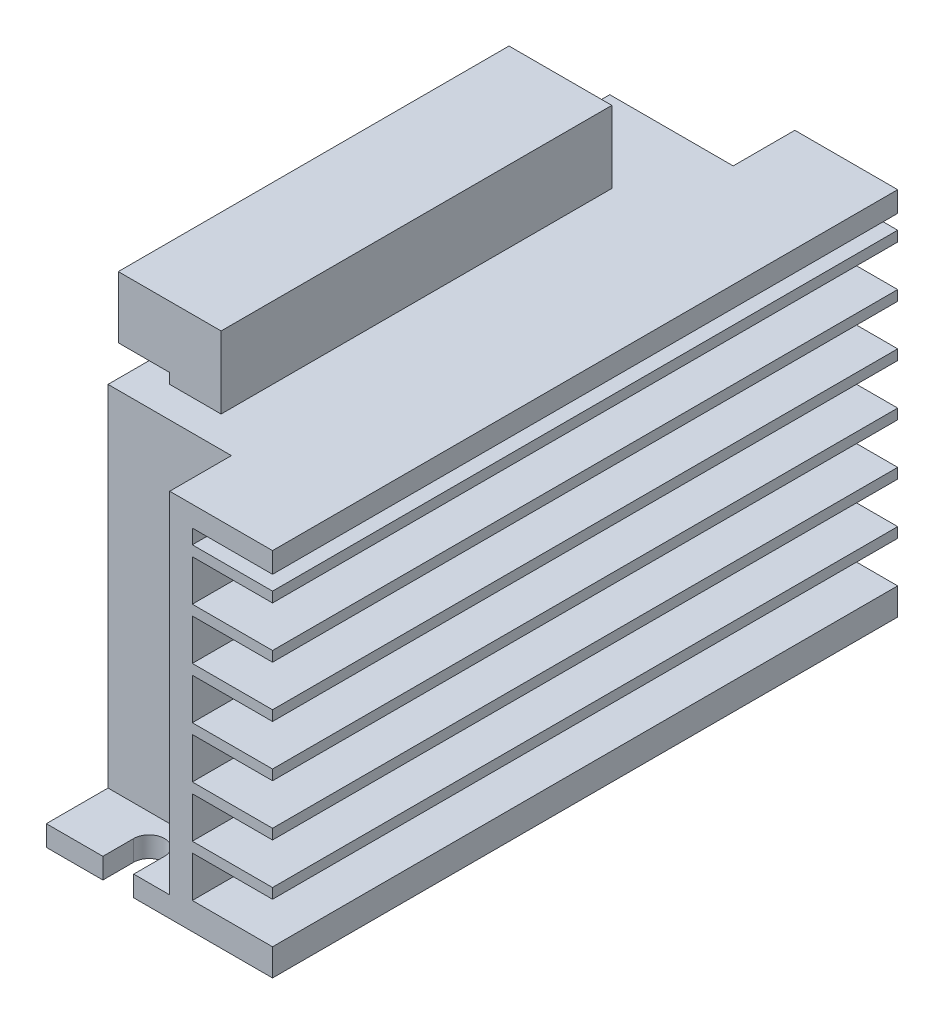
SolidWorks part; units mm, degrees
ref_plane "Front Plane" through (0, 0, 0) normal (0, 0, 1) x (1, 0, 0)
ref_plane "Top Plane" through (0, 0, 0) normal (0, 1, 0) x (1, 0, 0)
ref_plane "Right Plane" through (0, 0, 0) normal (1, 0, 0) x (0, 0, -1)
sketch "Sketch1" plane through (0, 0, 0) normal (0, 1, 0) x (1, 0, 0)
  line L0 (11.1125, 86.5187) -> (11.1125, 4.7625) construction
  line L1 (0, 0) -> (8.7313, 0)
  line L2 (0, 0) -> (0, 96.52)
  line L3 (0, 96.52) -> (8.7312, 96.52)
  line L4 (34.925, 0) -> (34.925, 96.52)
  line L5 (13.4937, 0) -> (34.925, 0)
  line L7 (8.7312, 91.7575) -> (8.7312, 96.52)
  line L9 (13.4937, 91.7575) -> (13.4937, 96.52)
  line L11 (8.7313, 4.7625) -> (8.7313, 0)
  line L13 (13.4937, 4.7625) -> (13.4937, 0)
  line L14 (13.4937, 96.52) -> (34.925, 96.52)
  arc A0 (8.7312, 91.7575) -> (13.4937, 91.7575) centre (11.1125, 91.7575) ccw
  arc A1 (13.4937, 4.7625) -> (8.7313, 4.7625) centre (11.1125, 4.7625) ccw
  dimension "D3" = 4.7625
  dimension "D6" = 4.7625
  dimension "D1" = 96.52
  dimension "D2" = 34.925
  dimension "D4" = 11.1125
  dimension "D5" = 4.7625
extrude "Boss-Extrude1" add sketch "Sketch1" along normal blind 57.15
sketch "Sketch2" plane through (0, 0, 0) normal (0, 0, 1) x (1, 0, 0)
  line L0 (13.4937, 0) -> (34.925, 0) construction
  line L1 (0, 57.15) -> (19.05, 57.15)
  line L2 (0, 57.15) -> (0, 3.175)
  line L3 (0, 3.175) -> (19.05, 3.175)
  line L4 (19.05, 57.15) -> (19.05, 3.175)
  dimension "D1" = 3.175
  dimension "D2" = 19.05
extrude "Cut-Extrude1" cut sketch "Sketch2" against normal blind 9.525
sketch "Sketch4" plane through (0, 0, -96.52) normal (0, 0, -1) x (-1, 0, 0)
  line L0 (0, 57.15) -> (0, 0) construction
  line L1 (0, 3.175) -> (-19.05, 3.175)
  line L2 (0, 3.175) -> (0, 57.15)
  line L3 (0, 57.15) -> (-19.05, 57.15)
  line L4 (-19.05, 3.175) -> (-19.05, 57.15)
  line L5 (-34.925, 57.15) -> (-13.4937, 57.15) construction
  line L6 (-34.925, 0) -> (-13.4937, 0) construction
  dimension "D1" = 3.175
  dimension "D2" = 19.05
extrude "Cut-Extrude2" cut sketch "Sketch4" against normal blind 9.525
sketch "Sketch5" plane through (0, 0, -96.52) normal (0, 0, -1) x (-1, 0, 0)
  line L0 (-34.925, 57.15) -> (-34.925, 0) construction
  line L1 (-34.925, 4.1741) -> (-22.5404, 4.1741)
  line L2 (-34.925, 4.1741) -> (-34.925, 10.5241)
  line L3 (-34.925, 10.5241) -> (-22.5404, 10.5241)
  line L4 (-22.5404, 4.1741) -> (-22.5404, 10.5241)
  line L5 (-28.7327, 0) -> (-28.7327, 57.15) construction
  line L6 (-34.925, 0) -> (-13.4937, 0) construction
  line L7 (-34.925, 57.15) -> (-19.05, 57.15) construction
  line L8 (-34.925, 18.4478) -> (-22.5404, 18.4478)
  line L9 (-34.925, 12.0978) -> (-34.925, 18.4478)
  line L10 (-34.925, 12.0978) -> (-22.5404, 12.0978)
  line L11 (-22.5404, 12.0978) -> (-22.5404, 18.4478)
  line L12 (-34.925, 26.3715) -> (-22.5404, 26.3715)
  line L13 (-34.925, 20.0215) -> (-34.925, 26.3715)
  line L14 (-34.925, 20.0215) -> (-22.5404, 20.0215)
  line L15 (-22.5404, 20.0215) -> (-22.5404, 26.3715)
  line L16 (-34.925, 34.2952) -> (-22.5404, 34.2952)
  line L17 (-34.925, 27.9452) -> (-34.925, 34.2952)
  line L18 (-34.925, 27.9452) -> (-22.5404, 27.9452)
  line L19 (-22.5404, 27.9452) -> (-22.5404, 34.2952)
  line L20 (-34.925, 42.2189) -> (-22.5404, 42.2189)
  line L21 (-34.925, 35.8689) -> (-34.925, 42.2189)
  line L22 (-34.925, 35.8689) -> (-22.5404, 35.8689)
  line L23 (-22.5404, 35.8689) -> (-22.5404, 42.2189)
  line L24 (-34.925, 50.1426) -> (-22.5404, 50.1426)
  line L25 (-34.925, 43.7926) -> (-34.925, 50.1426)
  line L26 (-34.925, 43.7926) -> (-22.5404, 43.7926)
  line L27 (-22.5404, 43.7926) -> (-22.5404, 50.1426)
  line L29 (-34.925, 51.7301) -> (-22.5404, 51.7301)
  line L30 (-34.925, 51.7301) -> (-34.925, 53.975)
  line L31 (-34.925, 53.975) -> (-22.5404, 53.975)
  line L32 (-22.5404, 51.7301) -> (-22.5404, 53.975)
  dimension "D1" = 6.35
  dimension "D2" = 3.175
  dimension "D3" = 6
  dimension "D4" = 1.5875
extrude "Cut-Extrude3" cut sketch "Sketch5" against normal up to surface (96.52 mm away) up to face at (22.4896, 20.1083, 0)
sketch "Sketch6" plane through (0, 57.15, 0) normal (0, 1, 0) x (1, 0, 0)
  line L0 (0, 86.995) -> (0, 9.525) construction
  line L1 (4.7625, 74.6106) -> (12.7, 74.6106)
  line L2 (4.7625, 74.6106) -> (4.7625, 14.2856)
  line L3 (4.7625, 14.2856) -> (12.7, 14.2856)
  line L4 (12.7, 74.6106) -> (12.7, 14.2856)
  line L5 (34.925, 48.26) -> (0, 48.26) construction
  line L6 (34.925, 0) -> (34.925, 96.52) construction
  line L7 (4.7625, 44.4481) -> (12.7, 44.4481) construction
  dimension "D1" = 7.9375
  dimension "D2" = 60.325
  dimension "D3" = 4.7625
extrude "Boss-Extrude2" add sketch "Sketch6" along normal blind 1.5875
sketch "Sketch7" plane through (0, 58.7375, 0) normal (0, 1, 0) x (1, 0, 0)
  line L1 (12.7, 14.2856) -> (-3.175, 14.2856)
  line L2 (12.7, 14.2856) -> (12.7, 74.6106)
  line L3 (12.7, 74.6106) -> (-3.175, 74.6106)
  line L4 (-3.175, 14.2856) -> (-3.175, 74.6106)
  dimension "D1" = 15.875
extrude "Boss-Extrude3" add sketch "Sketch7" along normal blind 9.525
